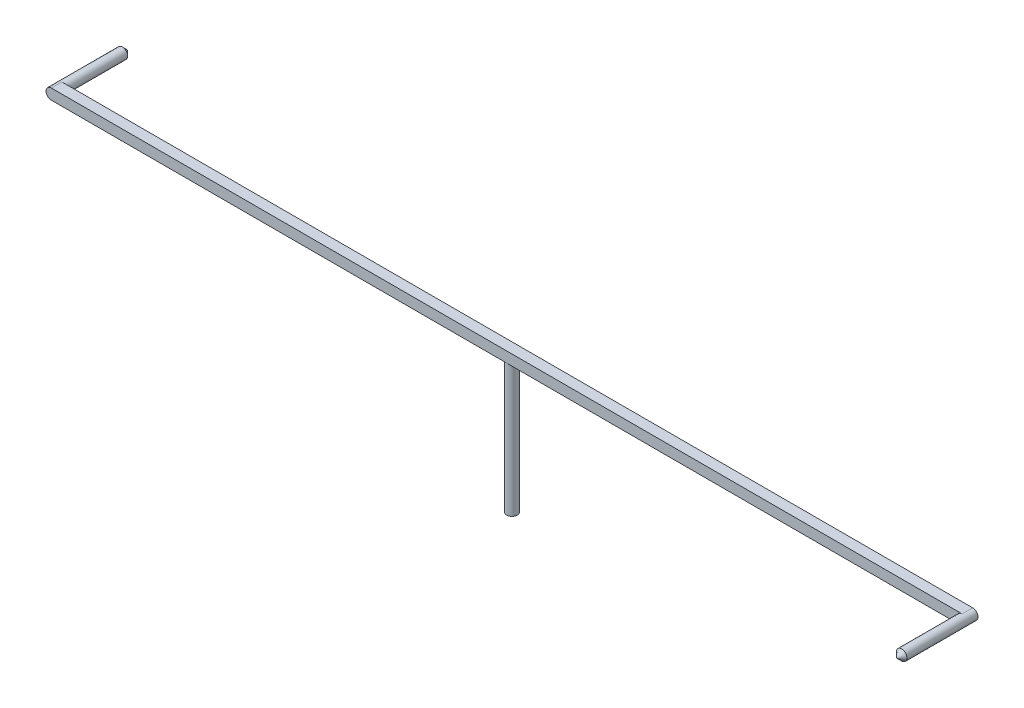
SolidWorks part; units mm, degrees
ref_plane "前视基准面" through (0, 0, 0) normal (0, 0, 1) x (1, 0, 0)
ref_plane "上视基准面" through (0, 0, 0) normal (0, 1, 0) x (1, 0, 0)
ref_plane "右视基准面" through (0, 0, 0) normal (1, 0, 0) x (0, 0, -1)
sketch "草图1" plane through (0, 0, 0) normal (0, 1, 0) x (1, 0, 0)
  circle A0 centre (0, 0) radius 0.4
  dimension "D1" = 0.8
extrude "凸台-拉伸1" add sketch "草图1" along normal blind 10
sketch "草图2" plane through (0, 10, 0) normal (0, 1, 0) x (1, 0, 0)
  line L1 (-35, 0.4) -> (35, 0.4)
  line L2 (-35, 0.4) -> (-35, -0.4)
  line L3 (-35, -0.4) -> (35, -0.4)
  line L4 (35, 0.4) -> (35, -0.4)
  circle A0 centre (0, 0) radius 0.4 construction
  dimension "D1" = 35
  dimension "D2" = 35
extrude "凸台-拉伸2" add sketch "草图2" along normal blind 0.8
fillet "圆角1" radius 0.4 4 edges at (35, 10, 0) (35, 10.8, 0) (-35, 10, 0) (-35, 10.8, 0)
sketch "草图3" plane through (0, 0, 0.4) normal (0, 0, 1) x (1, 0, 0)
  circle A0 centre (34.6, 10.4) radius 0.4
  dimension "D1" = 0.8
extrude "凸台-拉伸3" add sketch "草图3" along normal blind 5
sketch "草图4" plane through (0, 0, -0.4) normal (0, 0, -1) x (-1, 0, 0)
  circle A0 centre (34.6, 10.4) radius 0.4
  dimension "D1" = 0.8
extrude "凸台-拉伸4" add sketch "草图4" along normal blind 5
chamfer "倒角1" distance 0.4 angle 45 2 edges at (-35, 10.4, -5.4) (35, 10.4, 5.4)
